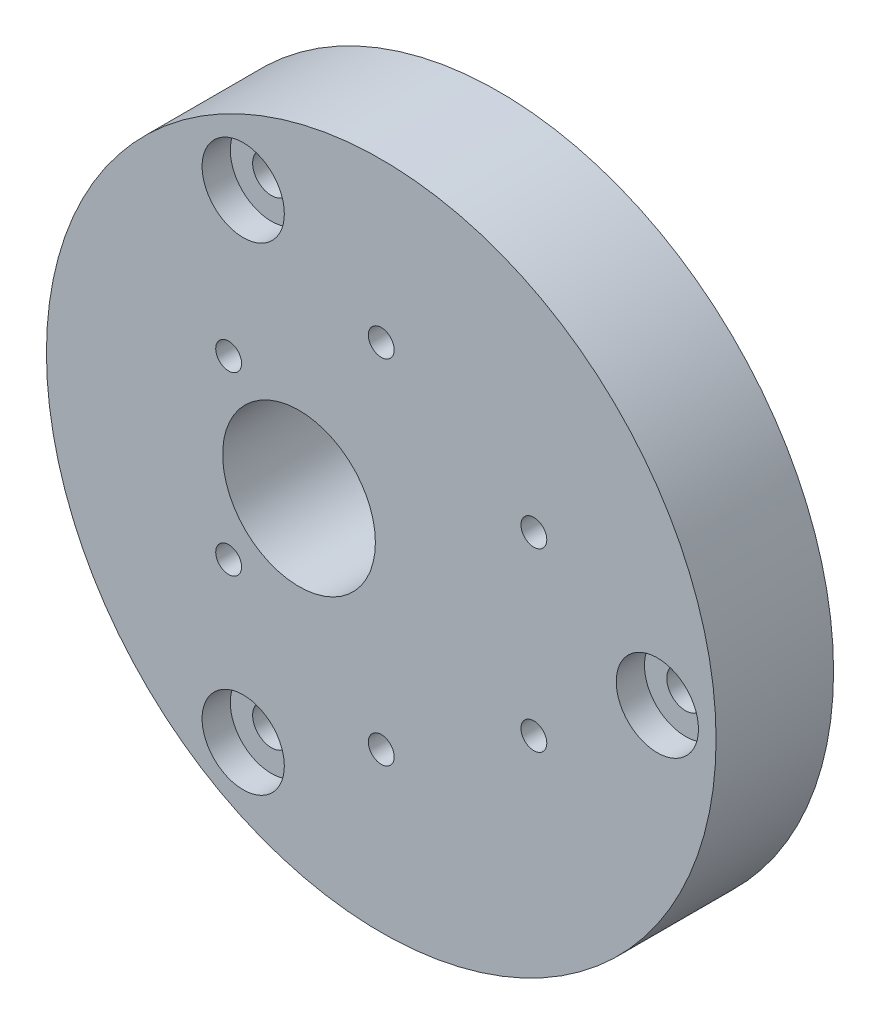
SolidWorks part; units mm, degrees
ref_plane "Alzado" through (0, 0, 0) normal (0, 0, 1) x (1, 0, 0)
ref_plane "Planta" through (0, 0, 0) normal (0, 1, 0) x (1, 0, 0)
ref_plane "Vista lateral" through (0, 0, 0) normal (1, 0, 0) x (0, 0, -1)
sketch "Croquis1" plane through (0, 0, 0) normal (0, 0, 1) x (1, 0, 0)
  line L0 (0, 0) -> (28.5, 0) construction
  line L1 (0, 0) -> (-7, 0) construction
  circle A0 centre (0, 0) radius 18.5
  circle A1 centre (0, 0) radius 28.5
  circle A2 centre (0, 0) radius 15 construction
  circle A3 centre (15, 0) radius 2.5
  circle A4 centre (0, 0) radius 23.5 construction
  circle A5 centre (23.5, 0) radius 2.5
  circle A6 centre (-7, 0) radius 6.5
  dimension "D1" = 37
  dimension "D3" = 30
  dimension "D4" = 5
  dimension "D6" = 5
  dimension "D8" = 13
  dimension "D7" = 7
  dimension "D2" = 10
  dimension "D5" = 5
extrude "Saliente-Extruir1" add sketch "Croquis1" along normal blind 10 contours A1 A5 A0 | A0 A3 | A5 | A3 region at (0.6877, 0, 0) region at (-27.6939, 0, 0) region at (15, 0, 0) region at (23.5, 0, 0)
sketch "Croquis2" plane through (0, 0, 10) normal (0, 0, 1) x (1, 0, 0)
  line L0 (0, 0) -> (28.5, 0) construction
  circle A0 centre (0, 0) radius 15 construction
  circle A1 centre (0, 0) radius 18.5 construction
  circle A2 centre (0, 0) radius 23.5 construction
  circle A3 centre (0, 0) radius 28.5 construction
  circle A4 centre (15, 0) radius 2.5
  circle A5 centre (23.5, 0) radius 2.5
  point P12 (23.5, 0)
  dimension "D1" = 30
  dimension "D2" = 37
  dimension "D4" = 5
  dimension "D5" = 5
  dimension "D3" = 5
hole_wizard "Refrentado para tornillo con cabeza troncocónica de M31" positions "Croquis2" profile "Croquis4" counterbore size "M3" standard "Ansi Metric"
sketch "Croquis4" plane through (23.5, 0, 10) normal (1, 0, 0) x (0, -1, 0)
  line L0 (0, 0) -> (0, 20.9614)
  line L1 (0, 20.9614) -> (1.6, 20)
  line L2 (1.6, 20) -> (1.6, 2.4)
  line L3 (1.6, 2.4) -> (3.5, 2.4)
  line L4 (3.5, 2.4) -> (3.5, 0)
  line L5 (3.5, 0) -> (0, 0)
  line L10 (0, 20.9614) -> (-1.6, 20) construction
  line L11 (0, -6.35) -> (0, 107.95) construction
  dimension "Diámetro de taladro" = 3.2
  dimension "Profundidad de taladro" = 20
  dimension "Diámetro de refrentado" = 7
  dimension "Profundidad de refrentado" = 2.4
  dimension "Ángulo de perforador" = 118
pattern_circular "MatrizC2" count 3 over 360 about axis through (0, 0, 10) along (0, 0, -1) of "Refrentado para tornillo con cabeza troncocónica de M31"
sketch "Croquis8" plane through (0, 0, 0) normal (0, 0, -1) x (-1, 0, 0)
  line L0 (0, 0) -> (-15, 0) construction
  line L1 (0, 0) -> (-12.9904, 7.5) construction
  circle A0 centre (0, 0) radius 15 construction
  circle A1 centre (-12.9904, 7.5) radius 2.5
  point P5 (-12.9904, 7.5)
  dimension "D1" = 30
  dimension "D3" = 5
  dimension "D2" = 30
hole_wizard "Refrentado para tornillo con cabeza troncocónica de M21" positions "Croquis8" profile "Croquis9" counterbore size "M2" standard "Ansi Metric"
sketch "Croquis9" plane through (12.9904, 7.5, 0) normal (1, 0, 0) x (0, 1, 0)
  line L0 (0, 0) -> (0, 20.6609)
  line L1 (0, 20.6609) -> (1.1, 20)
  line L2 (1.1, 20) -> (1.1, 1.6)
  line L3 (1.1, 1.6) -> (2.5, 1.6)
  line L4 (2.5, 1.6) -> (2.5, 0)
  line L5 (2.5, 0) -> (0, 0)
  line L10 (0, 20.6609) -> (-1.1, 20) construction
  line L11 (0, -6.35) -> (0, 107.95) construction
  dimension "Diámetro de taladro" = 2.2
  dimension "Profundidad de taladro" = 20
  dimension "Diámetro de refrentado" = 5
  dimension "Profundidad de refrentado" = 1.6
  dimension "Ángulo de perforador" = 118
pattern_circular "MatrizC3" count 6 over 360 about axis through (0, 0, 10) along (0, 0, -1) of "Refrentado para tornillo con cabeza troncocónica de M21" reverse direction yes
